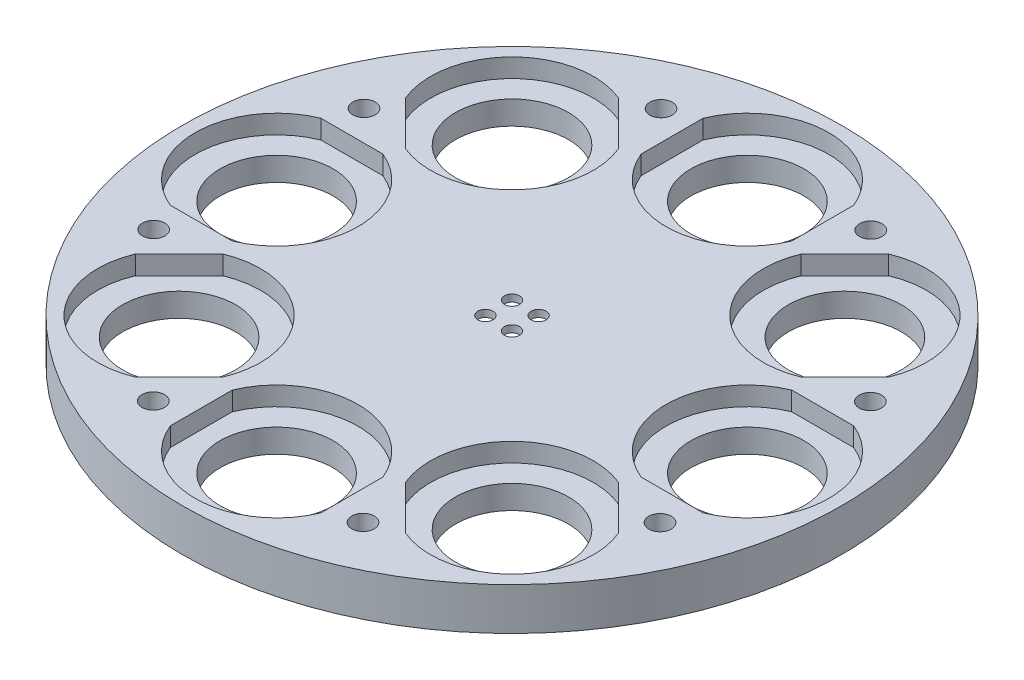
SolidWorks part; units mm, degrees
ref_plane "Front Plane" through (0, 0, 0) normal (0, 0, 1) x (1, 0, 0)
ref_plane "Top Plane" through (0, 0, 0) normal (0, 1, 0) x (1, 0, 0)
ref_plane "Right Plane" through (0, 0, 0) normal (1, 0, 0) x (0, 0, -1)
sketch "Sketch1" plane through (0, 0, 0) normal (0, 1, 0) x (1, 0, 0)
  line L0 (70, 0) -> (50, 0) construction
  circle A0 centre (0, 0) radius 70
  circle A1 centre (50, 0) radius 12
  circle A2 centre (35.3553, -35.3553) radius 12
  circle A3 centre (0, -50) radius 12
  circle A4 centre (-35.3553, -35.3553) radius 12
  circle A5 centre (-50, 0) radius 12
  circle A6 centre (-35.3553, 35.3553) radius 12
  circle A7 centre (0, 50) radius 12
  circle A8 centre (35.3553, 35.3553) radius 12
  point P23 (0, 0)
  dimension "D1" = 140
  dimension "D3" = 24
  dimension "D2" = 20
  dimension "D4" = 8
extrude "Boss-Extrude1" add sketch "Sketch1" along normal blind 25
sketch "Sketch2" plane through (0, 25, 0) normal (0, 1, 0) x (1, 0, 0)
  line L0 (50, 0) -> (50, 16) construction
  line L1 (50, 16) -> (43.4205, 16)
  line L2 (50, 16) -> (56.5795, 16)
  line L3 (32.7, 0) -> (67.3, 0) construction
  line L4 (50, -16) -> (56.5795, -16)
  line L5 (50, -16) -> (43.4205, -16)
  line L6 (46.669, -24.0416) -> (42.0166, -19.3892)
  line L7 (24.0416, -46.669) -> (19.3892, -42.0166)
  line L8 (24.0416, -46.669) -> (28.694, -51.3215)
  line L9 (46.669, -24.0416) -> (51.3215, -28.694)
  line L10 (16, -50) -> (16, -43.4205)
  line L11 (-16, -50) -> (-16, -43.4205)
  line L12 (-16, -50) -> (-16, -56.5795)
  line L13 (16, -50) -> (16, -56.5795)
  line L14 (-24.0416, -46.669) -> (-19.3892, -42.0166)
  line L15 (-46.669, -24.0416) -> (-42.0166, -19.3892)
  line L16 (-46.669, -24.0416) -> (-51.3215, -28.694)
  line L17 (-24.0416, -46.669) -> (-28.694, -51.3215)
  line L18 (-50, -16) -> (-43.4205, -16)
  line L19 (-50, 16) -> (-43.4205, 16)
  line L20 (-50, 16) -> (-56.5795, 16)
  line L21 (-50, -16) -> (-56.5795, -16)
  line L22 (-46.669, 24.0416) -> (-42.0166, 19.3892)
  line L23 (-24.0416, 46.669) -> (-19.3892, 42.0166)
  line L24 (-24.0416, 46.669) -> (-28.694, 51.3215)
  line L25 (-46.669, 24.0416) -> (-51.3215, 28.694)
  line L26 (-16, 50) -> (-16, 43.4205)
  line L27 (16, 50) -> (16, 43.4205)
  line L28 (16, 50) -> (16, 56.5795)
  line L29 (-16, 50) -> (-16, 56.5795)
  line L30 (24.0416, 46.669) -> (19.3892, 42.0166)
  line L31 (46.669, 24.0416) -> (42.0166, 19.3892)
  line L32 (46.669, 24.0416) -> (51.3215, 28.694)
  line L33 (24.0416, 46.669) -> (28.694, 51.3215)
  arc A0 (43.4205, 16) -> (43.4205, -16) centre (50, 0) ccw
  arc A1 (56.5795, -16) -> (56.5795, 16) centre (50, 0) ccw
  arc A2 (42.0166, -19.3892) -> (19.3892, -42.0166) centre (35.3553, -35.3553) ccw
  arc A3 (28.694, -51.3215) -> (51.3215, -28.694) centre (35.3553, -35.3553) ccw
  arc A4 (16, -43.4205) -> (-16, -43.4205) centre (0, -50) ccw
  arc A5 (-16, -56.5795) -> (16, -56.5795) centre (0, -50) ccw
  arc A6 (-19.3892, -42.0166) -> (-42.0166, -19.3892) centre (-35.3553, -35.3553) ccw
  arc A7 (-51.3215, -28.694) -> (-28.694, -51.3215) centre (-35.3553, -35.3553) ccw
  arc A8 (-43.4205, -16) -> (-43.4205, 16) centre (-50, 0) ccw
  arc A9 (-56.5795, 16) -> (-56.5795, -16) centre (-50, 0) ccw
  arc A10 (-42.0166, 19.3892) -> (-19.3892, 42.0166) centre (-35.3553, 35.3553) ccw
  arc A11 (-28.694, 51.3215) -> (-51.3215, 28.694) centre (-35.3553, 35.3553) ccw
  arc A12 (-16, 43.4205) -> (16, 43.4205) centre (0, 50) ccw
  arc A13 (16, 56.5795) -> (-16, 56.5795) centre (0, 50) ccw
  arc A14 (19.3892, 42.0166) -> (42.0166, 19.3892) centre (35.3553, 35.3553) ccw
  arc A15 (51.3215, 28.694) -> (28.694, 51.3215) centre (35.3553, 35.3553) ccw
  point P61 (0, 0)
  dimension "D1" = 34.6
  dimension "D2" = 16
  dimension "D3" = 8
extrude "Cut-Extrude1" cut sketch "Sketch2" against normal blind 10
ref_plane "Plane1" through (0, 10, 0) normal (0, 1, 0) x (1, 0, 0)
split "Split1" trim tools "Plane1" bodies to split 102 resulting bodies 103 104
delete or keep bodies "Body-Delete/Keep 1" type delete bodies bodies 104
sketch "Sketch3" plane through (0, 10, 0) normal (0, -1, 0) x (1, 0, 0)
  circle A0 centre (0, 0) radius 20
  dimension "D1" = 40
extrude "Cut-Extrude2" cut sketch "Sketch3" against normal blind 7.5
sketch "Sketch4" plane through (0, 25, 0) normal (0, 1, 0) x (1, 0, 0)
  circle A0 centre (0, 0) radius 70
extrude "Cut-Extrude3" cut sketch "Sketch4" against normal blind 6
sketch "Sketch5" plane through (0, 17.5, 0) normal (0, -1, 0) x (1, 0, 0)
  circle A0 centre (2.8254, 2.8314) radius 1.6
  circle A1 centre (2.8314, -2.8254) radius 1.6
  circle A2 centre (-2.8254, -2.8314) radius 1.6
  circle A3 centre (-2.8314, 2.8254) radius 1.6
  dimension "D1" = 3.2
extrude "Cut-Extrude4" cut sketch "Sketch5" against normal through all
sketch "Sketch7" plane through (0, 19, 0) normal (0, 1, 0) x (1, 0, 0)
  circle A0 centre (-22.2295, 53.882) radius 2.3813
  circle A1 centre (22.3817, 53.819) radius 2.3813
  circle A2 centre (53.882, 22.2295) radius 2.3813
  circle A3 centre (53.819, -22.3817) radius 2.3813
  circle A4 centre (22.2295, -53.882) radius 2.3813
  circle A5 centre (-22.3817, -53.819) radius 2.3813
  circle A6 centre (-53.882, -22.2295) radius 2.3812
  circle A7 centre (-53.819, 22.3817) radius 2.3812
  point P20 (0, 0)
  dimension "D1" = 4.7625
  dimension "D2" = 8
extrude "Cut-Extrude5" cut sketch "Sketch7" against normal through all
sketch "Sketch8" plane through (0, 19, 0) normal (0, 1, 0) x (1, 0, 0)
  line L2 (-16, 56.5795) -> (-16, 43.4205)
  line L3 (16, 43.4205) -> (16, 56.5795)
  line L4 (-16, 56.5795) -> (-16, 43.4205)
  line L5 (16, 43.4205) -> (16, 56.5795)
  circle A0 centre (0, 50) radius 12 construction
  circle A1 centre (0, 50) radius 12
  arc A2 (16, 56.5795) -> (-16, 56.5795) centre (0, 50) ccw
  arc A3 (-16, 43.4205) -> (16, 43.4205) centre (0, 50) ccw
  arc A4 (16, 56.5795) -> (-16, 56.5795) centre (0, 50) ccw
  arc A5 (-16, 43.4205) -> (16, 43.4205) centre (0, 50) ccw
  dimension "D1" = 0
